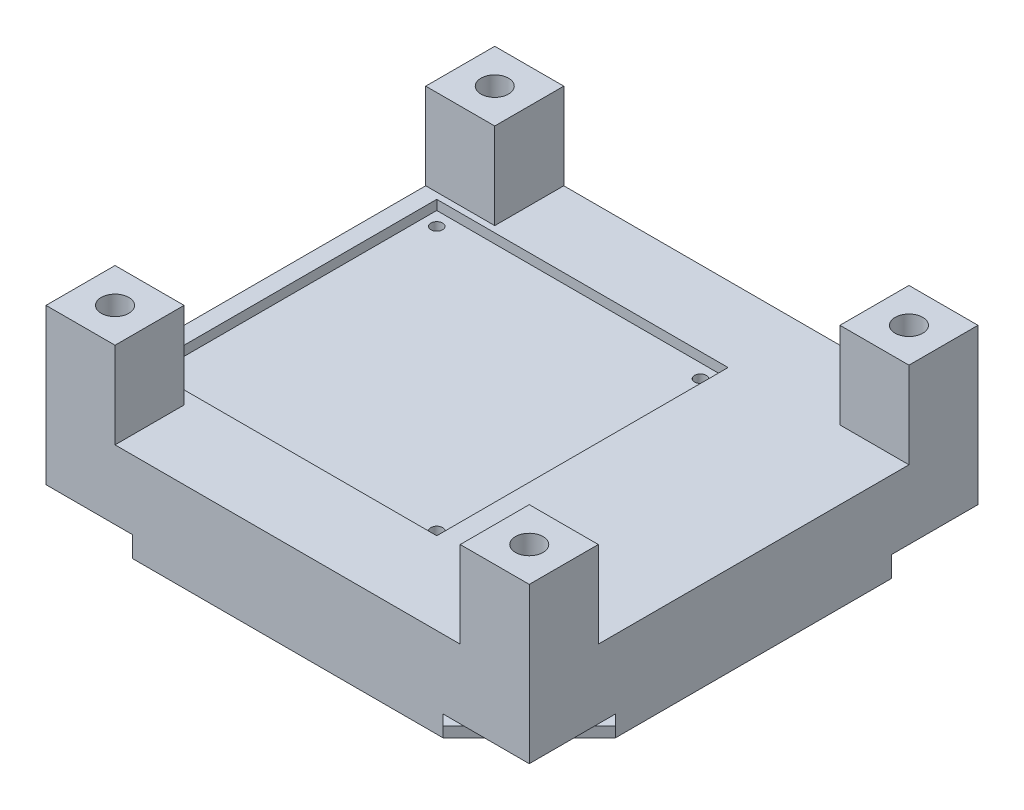
SolidWorks part; units mm, degrees
ref_plane "Front Plane" through (0, 0, 0) normal (0, 0, 1) x (1, 0, 0)
ref_plane "Top Plane" through (0, 0, 0) normal (0, 1, 0) x (1, 0, 0)
ref_plane "Right Plane" through (0, 0, 0) normal (1, 0, 0) x (0, 0, -1)
sketch "Sketch2" plane through (0, 0, 0) normal (0, 1, 0) x (1, 0, 0)
  line L1 (0, 0) -> (177.8, 0)
  line L2 (0, 0) -> (0, -165.1)
  line L3 (0, -165.1) -> (177.8, -165.1)
  line L4 (177.8, 0) -> (177.8, -165.1)
extrude "Boss-Extrude1" add sketch "Sketch2" along normal blind 25.4
ref_axis "Axis1" through (0, 25.4, 82.55) along (1, 0, 0)
ref_axis "Axis2" through (88.9, 25.4, 0) along (0, 0, 1)
ref_plane "Plane1" through (88.9, 0, 0) normal (-1, 0, 0) x (0, 0, 1)
ref_plane "Plane2" through (0, 0, 82.55) normal (0, 0, -1) x (-1, 0, 0)
sketch "Sketch6" plane through (0, 25.4, 0) normal (0, 1, 0) x (1, 0, 0)
  line L1 (0, 0) -> (25.4, 0)
  line L2 (0, 0) -> (0, -25.4)
  line L3 (0, -25.4) -> (25.4, -25.4)
  line L4 (25.4, 0) -> (25.4, -25.4)
extrude "Boss-Extrude2" add sketch "Sketch6" along normal blind 31.75
mirror "Mirror1" about plane through (0, 0, 82.55) normal (0, 0, -1) of "Boss-Extrude2"
mirror "Mirror2" about plane through (88.9, 0, 0) normal (-1, 0, 0) of "Mirror1"
sketch "Sketch9" plane through (0, 25.4, 0) normal (0, 1, 0) x (1, 0, 0)
  line L0 (0, -25.4) -> (25.4, -25.4) construction
  line L4 (6.35, -27.683) -> (113.538, -27.683)
  line L5 (6.35, -27.683) -> (6.35, -134.871)
  line L6 (6.35, -134.871) -> (113.538, -134.871)
  line L7 (113.538, -27.683) -> (113.538, -134.871)
  point P0 (12.7, -25.4)
extrude "Cut-Extrude3" cut sketch "Sketch9" against normal blind 3.556
sketch "Sketch10" plane through (0, 21.844, 0) normal (0, 1, 0) x (1, 0, 0)
  line L0 (6.35, -27.683) -> (11.43, -27.683)
  line L1 (113.538, -27.683) -> (6.35, -27.683) construction
  line L2 (11.43, -27.683) -> (11.43, -32.763)
  ellipse E0 centre (11.43, -32.763) end of major axis (12.6283, -30.9671) minor radius 2.159
  dimension "D1" = 5.08
  dimension "D2" = 5.08
ref_axis "Axis3" through (59.944, 25.4, 27.683) along (0, 0, 1)
ref_axis "Axis4" through (6.35, 25.4, 81.277) along (1, 0, 0)
ref_plane "Plane15" through (0, 0, 81.277) normal (0, 0, 1) x (1, 0, 0)
ref_plane "Plane16" through (59.944, 0, 0) normal (-1, 0, 0) x (0, 0, 1)
extrude "Cut-Extrude4" cut sketch "Sketch10" against normal blind 20.32 contours E0
mirror "Mirror3" about plane through (0, 0, 81.277) normal (0, 0, 1) of "Cut-Extrude4"
mirror "Mirror4" about plane through (59.944, 0, 0) normal (-1, 0, 0) of "Mirror3"
sketch "Sketch14" plane through (0, 57.15, 0) normal (0, 1, 0) x (1, 0, 0)
  circle A0 centre (12.7, -12.7) radius 5.08
extrude "Cut-Extrude5" cut sketch "Sketch14" against normal blind 20.32
mirror "Mirror5" about plane through (88.9, 0, 0) normal (-1, 0, 0) of "Cut-Extrude5"
mirror "Mirror6" about plane through (0, 0, 82.55) normal (0, 0, -1) of "Mirror5"
sketch "Sketch15" plane through (0, 0, 0) normal (0, -1, 0) x (-1, 0, 0)
  line L0 (-146.05, 0) -> (-31.75, 0)
  line L1 (-177.8, 0) -> (0, 0) construction
  line L2 (0, -133.35) -> (0, -31.75)
  line L3 (0, 0) -> (0, -165.1) construction
  line L4 (-31.75, 0) -> (0, -31.75)
  line L5 (13.97, -82.55) -> (-13.97, -82.55) construction
  line L6 (-31.75, -165.1) -> (0, -133.35)
  line L7 (-146.05, -165.1) -> (-31.75, -165.1)
  line L8 (-88.9, -13.97) -> (-88.9, 13.97) construction
  line L9 (-146.05, -165.1) -> (-177.8, -133.35)
  line L10 (-177.8, -133.35) -> (-177.8, -31.75)
  line L11 (-146.05, 0) -> (-177.8, -31.75)
  point P11 (0, -82.55)
  point P16 (-88.9, -165.1)
  point P19 (-88.9, 0)
extrude "Boss-Extrude3" add sketch "Sketch15" along normal blind 7.62
sketch "Sketch16" plane through (15.875, 0, 15.875) normal (-0.7071, 0, -0.7071) x (-0.7071, 0, 0.7071)
  line L0 (22.4506, -7.62) -> (22.4506, 0) construction
  line L1 (-22.4506, 0) -> (22.4506, 0)
  line L2 (-22.4506, 0) -> (-22.4506, -3.81)
  line L3 (-22.4506, -3.81) -> (22.4506, -3.81)
  line L4 (22.4506, 0) -> (22.4506, -3.81)
extrude "Cut-Extrude6" cut sketch "Sketch16" against normal blind 187.96
sketch "Sketch17" plane through (155.575, 0, 155.575) normal (0.7071, 0, 0.7071) x (0.7071, 0, -0.7071)
  line L0 (-13.4704, -7.62) -> (-13.4704, 0) construction
  line L1 (31.4309, 0) -> (-13.4704, 0)
  line L2 (31.4309, 0) -> (31.4309, -3.81)
  line L3 (31.4309, -3.81) -> (-13.4704, -3.81)
  line L4 (-13.4704, 0) -> (-13.4704, -3.81)
extrude "Cut-Extrude7" cut sketch "Sketch17" against normal blind 187.96
sketch "Sketch19" plane through (-66.675, 0, 66.675) normal (-0.7071, 0, 0.7071) x (0.7071, 0, 0.7071)
  line L0 (94.2927, -7.62) -> (94.2927, 0) construction
  line L1 (139.194, 0) -> (94.2927, 0)
  line L2 (139.194, 0) -> (139.194, -3.81)
  line L3 (139.194, -3.81) -> (94.2927, -3.81)
  line L4 (94.2927, 0) -> (94.2927, -3.81)
extrude "Cut-Extrude8" cut sketch "Sketch19" against normal blind 187.96
sketch "Sketch20" plane through (73.025, 0, -73.025) normal (0.7071, 0, -0.7071) x (-0.7071, 0, -0.7071)
  line L0 (-148.1742, -7.62) -> (-148.1742, 0) construction
  line L1 (-103.2729, 0) -> (-148.1742, 0)
  line L2 (-103.2729, 0) -> (-103.2729, -3.81)
  line L3 (-103.2729, -3.81) -> (-148.1742, -3.81)
  line L4 (-148.1742, 0) -> (-148.1742, -3.81)
extrude "Cut-Extrude9" cut sketch "Sketch20" against normal blind 187.96
sketch "Sketch23" plane through (0, 0, 0) normal (0, -1, 0) x (1, 0, 0)
  line L0 (0, 165.1) -> (177.8, 165.1) construction
  line L1 (88.9, 165.1) -> (88.9, 0) construction
  line L2 (31.75, 0) -> (146.05, 0) construction
  line L3 (50.9716, 82.3369) -> (88.9, 82.55) construction
  circle A0 centre (88.9, 82.55) radius 37.929
extrude "Cut-Extrude10" cut sketch "Sketch23" along normal blind 39.37
